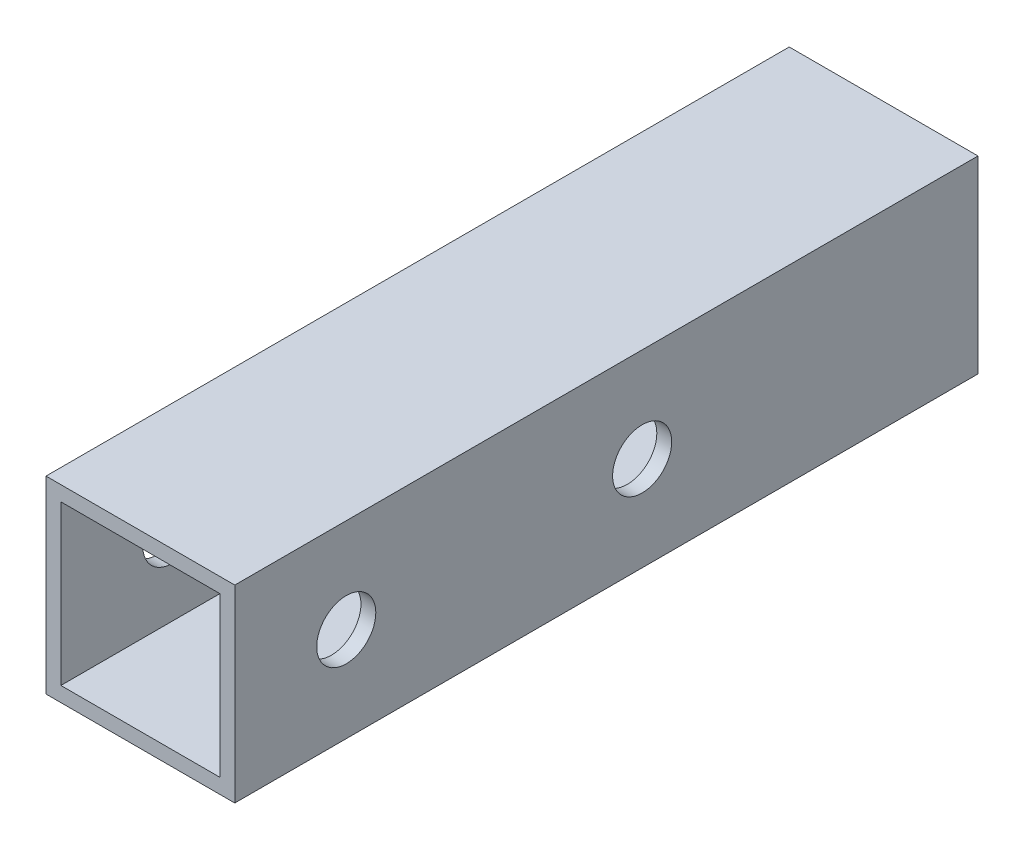
SolidWorks part; units mm, degrees
material "Acrylic (Medium-high impact)"
ref_plane "Front Plane" through (0, 0, 0) normal (0, 0, 1) x (1, 0, 0)
ref_plane "Top Plane" through (0, 0, 0) normal (0, 1, 0) x (1, 0, 0)
ref_plane "Right Plane" through (0, 0, 0) normal (1, 0, 0) x (0, 0, -1)
sketch "Sketch1" plane through (0, 0, 0) normal (0, 0, 1) x (1, 0, 0)
  line L1 (0, 0) -> (25.4, 0)
  line L2 (0, 0) -> (0, 25.4)
  line L3 (0, 25.4) -> (25.4, 25.4)
  line L4 (25.4, 0) -> (25.4, 25.4)
  line L5 (2, 23.4) -> (23.4, 23.4)
  line L6 (2, 23.4) -> (2, 2)
  line L7 (2, 2) -> (23.4, 2)
  line L8 (23.4, 23.4) -> (23.4, 2)
  dimension "D1" = 25.4
  dimension "D2" = 25.4
  dimension "D3" = 2
  dimension "D4" = 2
  dimension "D5" = 2
  dimension "D6" = 2
extrude "Boss-Extrude1" add sketch "Sketch1" along normal blind 100
sketch "Sketch2" plane through (25.4, 0, 0) normal (1, 0, 0) x (0, 0, -1)
  line L0 (0, 12.7) -> (-100, 12.7) construction
  line L1 (0, 0) -> (0, 25.4) construction
  line L2 (-100, 0) -> (-100, 25.4) construction
  circle A0 centre (-85, 12.7) radius 3.975
  circle A1 centre (-45.19, 12.7) radius 3.975
  dimension "D1" = 7.95
  dimension "D3" = 7.95
  dimension "D2" = 15
  dimension "D4" = 39.81
extrude "Cut-Extrude1" cut sketch "Sketch2" against normal blind 50
sketch "Sketch3" plane through (0, 0, 0) normal (0, -1, 0) x (1, 0, 0)
  line L0 (25.4, 100) -> (25.4, 0) construction
  line L1 (0, 0) -> (25.4, 0) construction
  line L2 (8.45, 70) -> (8.45, 10)
  line L3 (5.35, 10) -> (5.35, 70)
  circle A0 centre (6.9, 70) radius 1.55
  circle A1 centre (6.9, 10) radius 1.55
  dimension "D2" = 3.1
  dimension "D3" = 3.1
  dimension "D1" = 18.5
  dimension "D4" = 18.5
  dimension "D5" = 60
  dimension "D6" = 10
extrude "Cut-Extrude4" cut sketch "Sketch3" against normal blind 10 contours A1 L2 A0 L3 | A1 | A0 region at (6.9, 0, 70) region at (6.9, 0, 40) region at (6.9, 0, 10)
sketch "Sketch4" plane through (0, 0, 0) normal (0, -1, 0) x (1, 0, 0)
  circle A0 centre (7.5, 2.7657) radius 1.778
  circle A1 centre (17.5, 2.7657) radius 1.778
extrude "Cut-Extrude5" cut sketch "Sketch4" against normal blind 10
